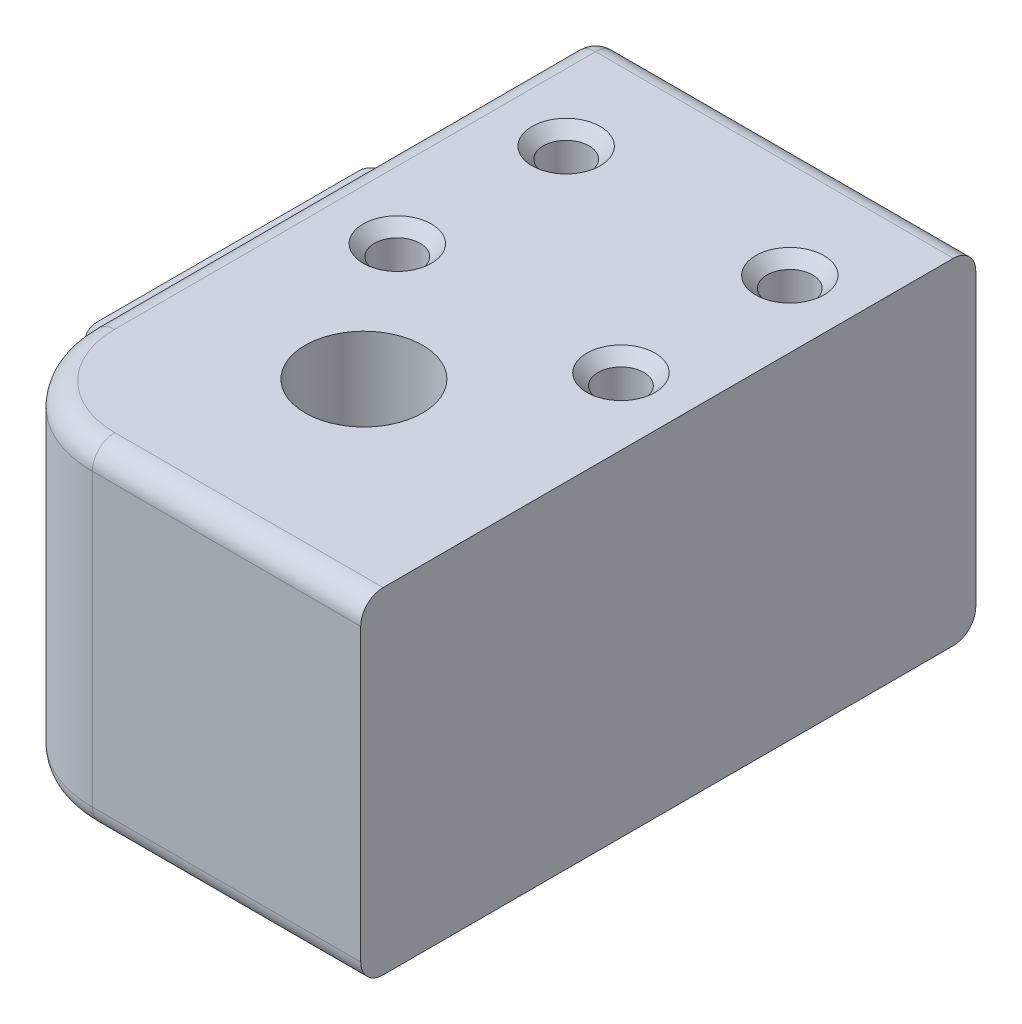
SolidWorks part; units mm, degrees
ref_plane "Front Plane" through (0, 0, 0) normal (0, 0, 1) x (1, 0, 0)
ref_plane "Top Plane" through (0, 0, 0) normal (0, 1, 0) x (1, 0, 0)
ref_plane "Right Plane" through (0, 0, 0) normal (1, 0, 0) x (0, 0, -1)
sketch "Sketch1" plane through (0, 0, 0) normal (0, 0, 1) x (1, 0, 0)
  line L1 (17, -15) -> (-17, -15)
  line L2 (17, -15) -> (17, 15)
  line L3 (17, 15) -> (-17, 15)
  line L4 (-17, -15) -> (-17, 15)
  dimension "D1" = 34
  dimension "D2" = 30
  dimension "D3" = 15
  dimension "D4" = 17
extrude "Boss-Extrude1" add sketch "Sketch1" along normal blind 55
sketch "Sketch2" plane through (0, 0, 0) normal (0, 0, -1) x (-1, 0, 0)
  line L0 (-17, -15) -> (-17, 15) construction
  line L1 (17, -15) -> (-17, -15) construction
  circle A4 centre (-12, 9) radius 2 construction
  circle A5 centre (-12, -9) radius 2 construction
  circle A6 centre (12, -9) radius 2 construction
  circle A7 centre (12, 9) radius 2 construction
  circle A8 centre (12, -9) radius 2.1
  circle A9 centre (12, 9) radius 2.1
  circle A10 centre (-12, -9) radius 2.1
  circle A11 centre (-12, 9) radius 2.1
  dimension "D1" = 4
  dimension "D2" = 5
  dimension "D3" = 29
  dimension "D4" = 6
  dimension "D5" = 24
  dimension "D6" = 0.1
extrude "Cut-Extrude1" cut sketch "Sketch2" against normal blind 6
sketch "Sketch5" plane through (0, -15, 0) normal (0, -1, 0) x (1, 0, 0)
  line L0 (17, 55) -> (17, 0) construction
  line L1 (-17, 0) -> (17, 0) construction
  circle A1 centre (0, 37.7136) radius 11 construction
  circle A3 centre (0, 37.7136) radius 11.15
  dimension "D1" = 22
  dimension "D2" = 17
  dimension "D3" = 37.7136
  dimension "D4" = 0.15
extrude "Cut-Extrude2" cut sketch "Sketch5" against normal blind 12.5
sketch "Sketch6" plane through (0, 15, 0) normal (0, 1, 0) x (1, 0, 0)
  line L0 (-17, -55) -> (-17, 0) construction
  line L1 (17, 0) -> (-17, 0) construction
  circle A1 centre (0, -37.7136) radius 5.1 construction
  circle A2 centre (0, -37.7136) radius 5.25
  dimension "D1" = 10.2
  dimension "D2" = 17
  dimension "D3" = 37.7136
  dimension "D4" = 0.15
extrude "Cut-Extrude3" cut sketch "Sketch6" against normal blind 17.5
sketch "Sketch7" plane through (0, -2.5, 0) normal (0, -1, 0) x (1, 0, 0)
  circle A4 centre (7.9785, 38.3002) radius 1.75 construction
  circle A5 centre (-0.5866, 45.6921) radius 1.75 construction
  circle A6 centre (-7.9785, 37.127) radius 1.75 construction
  circle A7 centre (0.5866, 29.7351) radius 1.75 construction
  circle A8 centre (-7.9785, 37.127) radius 2.1
  circle A9 centre (-0.5866, 45.6921) radius 2.1
  circle A10 centre (7.9785, 38.3002) radius 2.1
  circle A11 centre (0.5866, 29.7351) radius 2.1
  circle A12 centre (0, 37.7136) radius 5.25 construction
  dimension "D2" = 4.2
  dimension "D3" = 0.5866
  dimension "D4" = 7.9785
  dimension "D5" = 0.5866
  dimension "D6" = 7.9785
  dimension "D7" = 0.5866
  dimension "D8" = 7.9785
  dimension "D9" = 0.5866
  dimension "D10" = 7.9785
  dimension "D1" = 0.35
extrude "Cut-Extrude4" cut sketch "Sketch7" against normal blind 6
chamfer "Chamfer1" distance 1 angle 45 4 edges at (7.9785, -2.5, 36.2002) (-0.5866, -2.5, 43.5921) (-7.9785, -2.5, 35.027) (0.5866, -2.5, 27.6351)
chamfer "Chamfer2" distance 1 angle 45 4 edges at (9.9, -9, 0) (-14.1, -9, 0) (-14.1, 9, 0) (9.9, 9, 0)
fillet "Fillet1" radius 10 1 edges at (-17, 0, 55)
fillet "Fillet2" radius 2 9 edges at (-17, 15, 22.5) (5, 15, 55) (5, -15, 55) (-17, -15, 22.5) (0, -15, 0) (-17, 0, 0) (0, 15, 0) (-14.0711, 15, 52.0711) (-14.0711, -15, 52.0711)
sketch "Sketch8" plane through (17, 0, 0) normal (1, 0, 0) x (0, 0, -1)
  line L1 (-45, 9) -> (-10, 9) construction
  line L2 (-45, 9) -> (-45, -9) construction
  line L3 (-45, -9) -> (-10, -9) construction
  line L4 (-10, 9) -> (-10, -9) construction
  line L5 (-45, 9) -> (-10, -9) construction
  line L6 (-45, -9) -> (-10, 9) construction
  line L7 (-53, 15) -> (-2, 15) construction
  circle A0 centre (-45, 9) radius 2.075
  circle A1 centre (-10, 9) radius 2.075
  circle A2 centre (-10, -9) radius 2.075
  circle A3 centre (-45, -9) radius 2.075
  point P0 (-27.5, 0)
  point P14 (-27.5, 15)
  dimension "D1" = 4.15
  dimension "D2" = 35
  dimension "D3" = 18
extrude "Cut-Extrude5" [suppressed] cut sketch "Sketch8" against normal blind 6.5
chamfer "Chamfer3" [suppressed] distance 1.5 angle 45
sketch "Sketch9" plane through (0, 0, 0) normal (0, 1, 0) x (1, 0, 0)
  line L0 (-17, -40.0491) -> (-24.3539, -40.0491)
  line L1 (-17, -2) -> (-17, -45) construction
  line L2 (-24.3539, -40.0491) -> (-24.3539, -12.7622)
  line L3 (-24.3539, -12.7622) -> (-17, -12.7622)
  line L4 (-17, -12.7622) -> (-17, -40.0491)
  line L5 (-20.6, -35) -> (-20.6, -19)
  circle A1 centre (-20.6, -35) radius 1.625
  circle A2 centre (-20.6, -19) radius 1.625
  dimension "D3" = 3.25
  dimension "D1" = 3.6
  dimension "D2" = 16
extrude "Boss-Extrude2" add sketch "Sketch9" along normal blind 3 from offset 4 contours L4 L3 L2 L0 A2 A1 region at (-20.6839, 0, 26.3521)
mirror "Mirror1" about plane through (0, 0, 0) normal (0, 1, 0) of "Boss-Extrude2"
fillet "Fillet3" radius 3 4 edges at (-24.3539, 5.5, 40.0491) (-17, 5.5, 40.0491) (-17, -5.5, 40.0491) (-24.3539, -5.5, 40.0491)
fillet "Fillet4" radius 1 4 edges at (-24.3539, 5.5, 12.7622) (-17, 5.5, 12.7622) (-17, -5.5, 12.7622) (-24.3539, -5.5, 12.7622)
sketch "Sketch10" plane through (0, 7, 0) normal (0, 1, 0) x (1, 0, 0)
  line L1 (-17.725, -20.6599) -> (-17.725, -17.3401)
  line L2 (-17.725, -17.3401) -> (-20.6, -15.6802)
  line L3 (-20.6, -15.6802) -> (-23.475, -17.3401)
  line L4 (-23.475, -17.3401) -> (-23.475, -20.6599)
  line L5 (-23.475, -20.6599) -> (-20.6, -22.3198)
  line L6 (-20.6, -22.3198) -> (-17.725, -20.6599)
  line L7 (-17.725, -36.6599) -> (-17.725, -33.3401)
  line L8 (-17.725, -33.3401) -> (-20.6, -31.6802)
  line L9 (-20.6, -31.6802) -> (-23.475, -33.3401)
  line L10 (-23.475, -33.3401) -> (-23.475, -36.6599)
  line L11 (-23.475, -36.6599) -> (-20.6, -38.3198)
  line L12 (-20.6, -38.3198) -> (-17.725, -36.6599)
  circle A0 centre (-20.6, -19) radius 2.875 construction
  circle A1 centre (-20.6, -35) radius 2.875 construction
  dimension "D1" = 5.75
extrude "Cut-Extrude6" cut sketch "Sketch10" against normal blind 2
ref_plane "Plane1" through (0, 0, 18.18) normal (0, 0, -1) x (-1, 0, 0)
sketch "Sketch13" plane through (0, -15, 0) normal (0, -1, 0) x (1, 0, 0)
  line L0 (-14.3, 18.18) -> (14.3, 18.18) construction
  line L1 (-9, 25.73) -> (11, 25.73) construction
  line L2 (-9, 25.73) -> (-9, 10.63) construction
  line L3 (-9, 10.63) -> (11, 10.63) construction
  line L4 (11, 25.73) -> (11, 10.63) construction
  line L5 (-15, 2) -> (17, 2) construction
  circle A0 centre (-9, 25.73) radius 2.05
  circle A1 centre (11, 25.73) radius 2.05
  circle A2 centre (-9, 10.63) radius 2.05
  circle A3 centre (11, 10.63) radius 2.05
  point P8 (-11.067, 7.3132)
  point P9 (13.1571, 23.4626)
  point P10 (11, 18.18)
  point P15 (1, 2)
  point P16 (1, 10.63)
  dimension "D1" = 4.1
  dimension "D2" = 5.5
  dimension "D3" = 20
extrude "Cut-Extrude7" cut sketch "Sketch13" against normal through all
chamfer "Chamfer4" distance 1 angle 45 8 edges at (11, -15, 23.68) (11, -15, 8.58) (-9, -15, 23.68) (-9, -15, 8.58) (11, 15, 8.58) (11, 15, 23.68) (-9, 15, 8.58) (-9, 15, 23.68)
